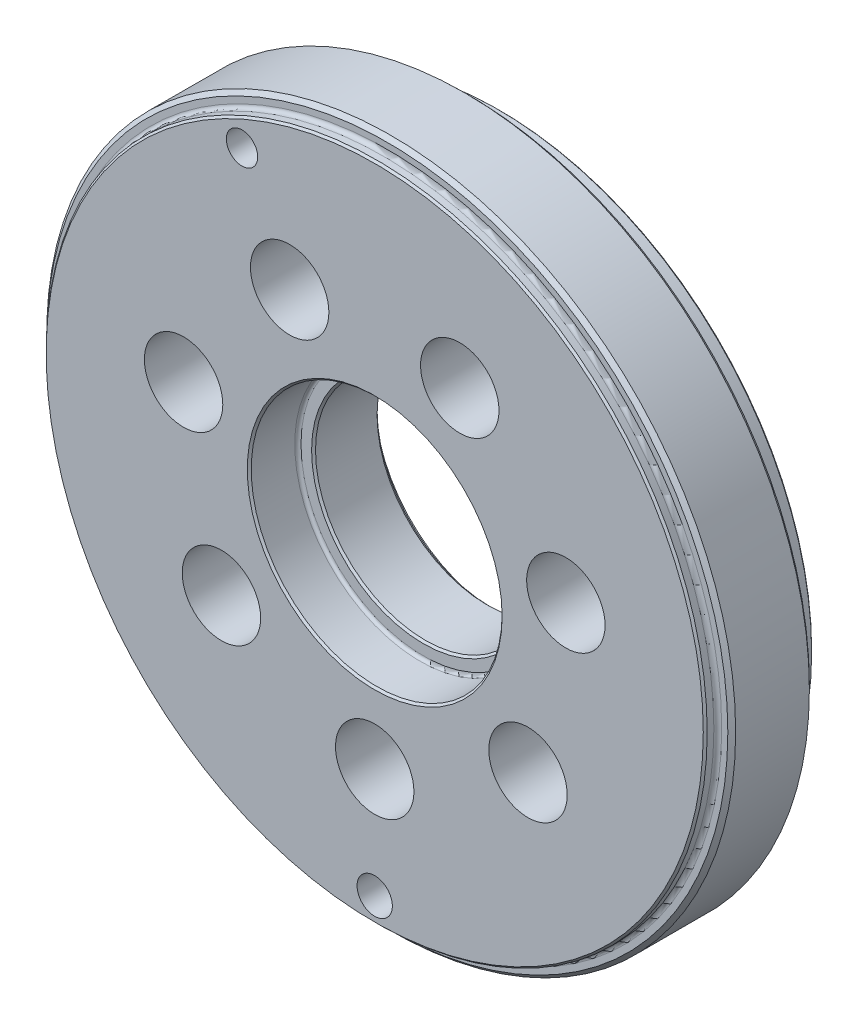
SolidWorks part; units mm, degrees
material "2P Cast Iron"
ref_plane "Front Plane" through (0, 0, 0) normal (0, 0, 1) x (1, 0, 0)
ref_plane "Top Plane" through (0, 0, 0) normal (0, 1, 0) x (1, 0, 0)
ref_plane "Right Plane" through (0, 0, 0) normal (1, 0, 0) x (0, 0, -1)
sketch "Sketch1" plane through (0, 0, 0) normal (0, 0, 1) x (1, 0, 0)
  line L0 (0, 0) -> (86.0326, 0) construction
  line L1 (0, 0) -> (0, 58.9688) construction
  circle A4 centre (0, 0) radius 14
  circle A5 centre (0, 0) radius 43.93
  dimension "D6" = 28
  dimension "D7" = 87.86
extrude "Extrude1" add sketch "Sketch1" against normal blind 16
sketch "Sketch13" plane through (0, 0, 0) normal (1, 0, 0) x (0, 0, -1)
  line L0 (0, 0) -> (24.7077, 0) construction
  line L1 (5.8, 16) -> (0.25, 16)
  line L2 (16, -43.93) -> (16, 43.93) construction
  line L3 (6.2, 15.6) -> (6.2, 14.25)
  line L4 (6.45, 14) -> (14.3, 14)
  line L5 (14.8, 14.5) -> (14.8, 15.6)
  line L6 (15.2, 16) -> (16, 16)
  line L7 (16, 39.72) -> (15.75, 39.97)
  line L9 (0.25, 16) -> (0, 16.25)
  line L10 (14.3, 14) -> (14.8, 14.5)
  line L11 (6.2, 14.25) -> (6.45, 14)
  line L12 (0, 41.9) -> (0.25, 42.15)
  line L13 (0, 43.93) -> (0, -43.93) construction
  line L14 (0, 16.25) -> (0, 41.9)
  line L15 (0.25, 42.15) -> (1.1, 42.15)
  line L16 (1.6, 42.65) -> (1.6, 50.0474)
  line L17 (1.6, 50.0474) -> (-4.8431, 50.0474)
  line L18 (0, 0) -> (19.0487, 0)
  line L19 (16, 16) -> (16, 39.72)
  line L20 (15.75, 39.97) -> (12.4, 39.97)
  line L21 (12, 40.37) -> (12, 50.0474)
  line L22 (12, 50.0474) -> (19.0487, 50.0474)
  line L23 (19.0487, 50.0474) -> (19.0487, 0)
  line L24 (-4.8431, 50.0474) -> (-4.8431, 0)
  line L25 (0, 0) -> (-4.8431, 0)
  arc A0 (5.8, 16) -> (6.2, 15.6) centre (5.8, 15.6) cw
  arc A1 (14.8, 15.6) -> (15.2, 16) centre (15.2, 15.6) cw
  arc A3 (1.1, 42.15) -> (1.6, 42.65) centre (1.1, 42.65) ccw
  arc A4 (12.4, 39.97) -> (12, 40.37) centre (12.4, 40.37) cw
  point P24 (0, 42.15)
  point P39 (16, 39.97)
  dimension "D6" = 0.4
  dimension "D14" = 0.25
  dimension "D18" = 0.4
  dimension "D20" = 0.5
  dimension "D1" = 32
  dimension "D2" = 32
  dimension "D3" = 100.0949
  dimension "D4" = 28
  dimension "D7" = 0.25
  dimension "D8" = 45
  dimension "D9" = 45
  dimension "D10" = 0.5
  dimension "D11" = 1.2
  dimension "D12" = 10.4
  dimension "D13" = 45
  dimension "D15" = 79.94
  dimension "D16" = 84.3
  dimension "D17" = 4
  dimension "D19" = 45
  dimension "D21" = 3.0487
  dimension "D22" = 4.8431
  dimension "D23" = 6.2
  dimension "D24" = 0.25
revolve "Cut-Revolve1" cut sketch "Sketch13" angle 360 about L0
sketch "Sketch9" plane through (0, 0, -16) normal (0, 0, -1) x (-1, 0, 0)
  line L0 (0, 0) -> (34.7, 0) construction
  line L1 (0, 0) -> (0, -40.1442) construction
  line L2 (-3, -23) -> (-3, -27)
  line L3 (3, -27) -> (3, -23)
  circle A0 centre (0, 0) radius 14 construction
  arc A1 (3, -23) -> (-3, -23) centre (0, -23) ccw
  arc A2 (-3, -27) -> (3, -27) centre (0, -27) ccw
  dimension "D1" = 3
  dimension "D2" = 10
  dimension "D3" = 27
  dimension "D4" = 6
extrude "Extrude7" cut sketch "Sketch9" against normal blind 2
sketch "Sketch18" plane through (0, 0, -16) normal (0, 0, -1) x (-1, 0, 0)
  line L0 (0, 0) -> (50.6333, 0) construction
  line L1 (0, 0) -> (0, -49.0418) construction
  line L2 (0, 0) -> (21.5214, -44.6896) construction
  line L3 (9.9793, -20.7223) -> (11.7149, -24.3262) construction
  line L4 (12.6822, -19.4206) -> (14.4178, -23.0245)
  line L5 (7.2764, -22.0239) -> (9.012, -25.6278)
  arc A2 (12.6822, -19.4206) -> (7.2764, -22.0239) centre (9.9793, -20.7223) ccw
  arc A3 (9.012, -25.6278) -> (14.4178, -23.0245) centre (11.7149, -24.3262) ccw
  arc A4 (3, -23) -> (-3, -23) centre (0, -23) ccw construction
  circle A5 centre (0, 0) radius 23 construction
  circle A6 centre (0, 0) radius 27 construction
  point P3 (10.8471, -22.5242)
  dimension "D1" = 25.714
extrude "Cut-Extrude5" cut sketch "Sketch18" against normal blind 0.6
pattern_circular "CirPattern3" count 7 over 360 about axis through (0, 0, -16) along (0, 0, 1) of "Cut-Extrude5"
sketch "Sketch10" plane through (0, 0, -14) normal (0, 0, -1) x (-1, 0, 0)
  line L0 (0, -20) -> (0, -30) construction
  arc A1 (-3, -27) -> (3, -27) centre (0, -27) ccw construction
  circle A2 centre (0, -25) radius 5
  arc A3 (3, -23) -> (-3, -23) centre (0, -23) ccw construction
  dimension "D1" = 10
extrude "Extrude8" cut sketch "Sketch10" against normal up to next
pattern_circular "CirPattern2" count 7 over 360 about axis through (0, 0, -16) along (0, 0, 1) of "Extrude8", "Extrude7"
sketch "Sketch17" plane through (0, 0, 0) normal (0, 0, -1) x (-1, 0, 0)
  line L0 (0, 0) -> (10.8471, 22.5242) construction
  line L1 (0, 0) -> (67.2556, 0) construction
  line L2 (0, 0) -> (0, -48.3478) construction
  circle A0 centre (0, -39) radius 2.25
  circle A1 centre (16.9215, 35.1378) radius 2
  circle A2 centre (0, 0) radius 39 construction
  dimension "D1" = 4.5
  dimension "D2" = 78
  dimension "D3" = 4
hole_wizard "Ø4.0 (4) Diameter Hole1" positions "Sketch22" profile "Sketch21" hole size "Ø4.0" standard "Ansi Metric"
sketch "Sketch22" plane through (0, 0, 0) normal (0, 0, 1) x (1, 0, 0)
  point P0 (-16.9215, 35.1378)
sketch "Sketch21" plane through (-16.9215, 35.1378, 0) normal (1, 0, 0) x (0, -1, 0)
  line L0 (0, 0) -> (0, 7.2017)
  line L1 (0, 7.2017) -> (2, 6)
  line L2 (2, 6) -> (2, 0)
  line L5 (2, 0) -> (0, 0)
  line L10 (0, 7.2017) -> (-2, 6) construction
  line L11 (0, -6.35) -> (0, 107.95) construction
  dimension "Hole Dia." = 4
  dimension "Hole Depth" = 6
  dimension "Drill Angle" = 118
hole_wizard "Ø4.5 (4.5) Diameter Hole2" positions "Sketch24" profile "Sketch23" hole size "Ø4.5" standard "Ansi Metric"
sketch "Sketch24" plane through (0, 0, 0) normal (0, 0, 1) x (1, 0, 0)
  point P0 (0, -39)
sketch "Sketch23" plane through (0, -39, 0) normal (1, 0, 0) x (0, -1, 0)
  line L0 (0, 0) -> (0, 14.8519)
  line L1 (0, 14.8519) -> (2.25, 13.5)
  line L2 (2.25, 13.5) -> (2.25, 0)
  line L5 (2.25, 0) -> (0, 0)
  line L10 (0, 14.8519) -> (-2.25, 13.5) construction
  line L11 (0, -6.35) -> (0, 107.95) construction
  dimension "Hole Dia." = 4.5
  dimension "Hole Depth" = 13.5
  dimension "Drill Angle" = 118
chamfer "Chamfer1" distance 0.5 angle 45 2 edges at (43.93, 0, -1.6) (-43.93, 0, -12)
